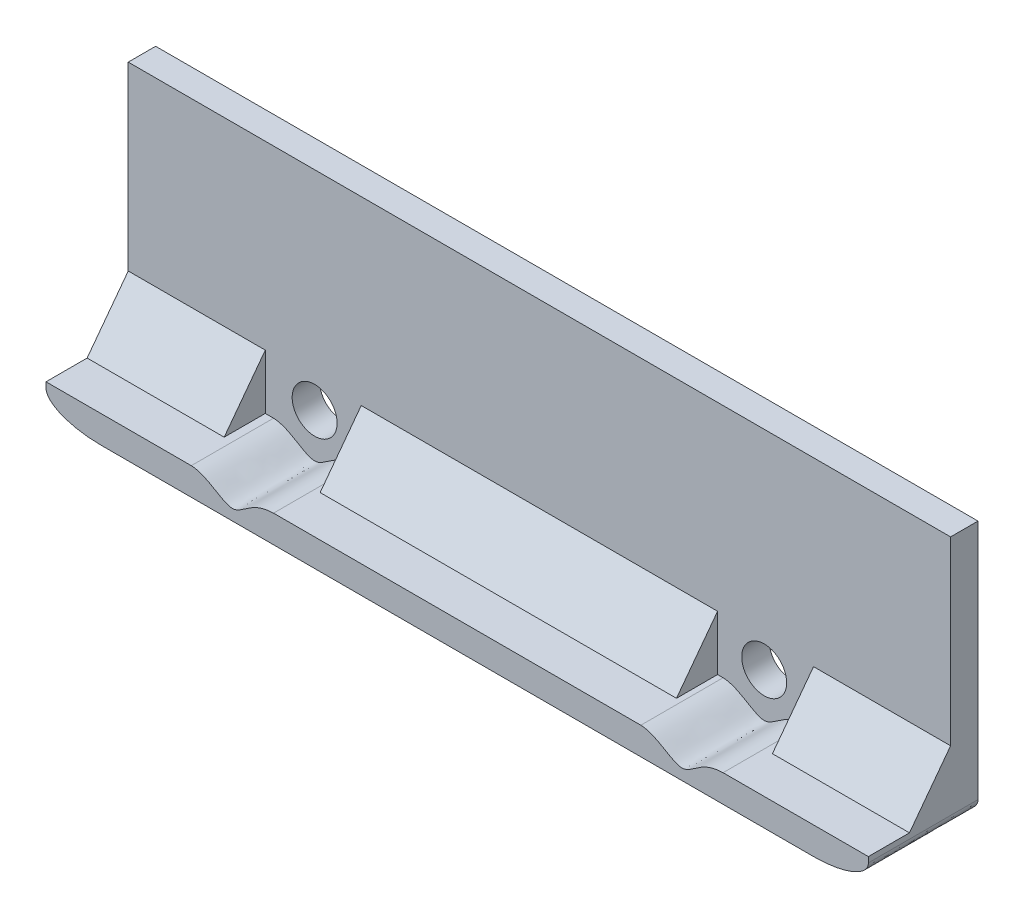
SolidWorks part; units mm, degrees
ref_plane "Front Plane" through (0, 0, 0) normal (0, 0, 1) x (1, 0, 0)
ref_plane "Top Plane" through (0, 0, 0) normal (0, 1, 0) x (1, 0, 0)
ref_plane "Right Plane" through (0, 0, 0) normal (1, 0, 0) x (0, 0, -1)
sketch "Sketch1" plane through (0, 0, 0) normal (0, 0, 1) x (1, 0, 0)
  line L0 (11.055, 0) -> (-11.055, 0) construction
  line L1 (-75, 0) -> (75, 0)
  line L2 (-75, 0) -> (-75, 48)
  line L3 (-75, 48) -> (75, 48)
  line L4 (75, 0) -> (75, 48)
  line L5 (0, 70.9447) -> (0, -59.6077) construction
  circle A0 centre (-41, 10) radius 4.1
  circle A1 centre (41, 10) radius 4.1
  dimension "D4" = 8.2
  dimension "D5" = 8.2
  dimension "D1" = 150
  dimension "D2" = 82
  dimension "D3" = 10
  dimension "D6" = 48
extrude "Boss-Extrude1" add sketch "Sketch1" along normal blind 5
sketch "Sketch2" plane through (0, 0, 0) normal (0, 0, 1) x (1, 0, 0)
  line L0 (55, 0) -> (-55, 0) construction
  line L1 (-75, 0) -> (75, 0)
  line L2 (-75, 0) -> (-75, 5)
  line L3 (-75, 5) -> (75, 5)
  line L4 (75, 0) -> (75, 5)
  line L5 (75, 0) -> (75, 48) construction
  line L6 (-41, 14.1) -> (-41, 5.9) construction
  line L7 (41, 14.1) -> (41, 5.9) construction
  circle A0 centre (-41, 10) radius 4.1 construction
  circle A1 centre (41, 10) radius 4.1 construction
  spline S0 degree 3 poles (-48.5, 5) (-45.5232, 4.8951) (-40.329, -0.8951) (-37.8188, 4.8951) (-33.5, 5) knots 0 0 0 0 0.5 1 1 1 1
  spline S1 degree 3 poles (33.5, 5) (36.4768, 4.8951) (41.671, -0.8951) (44.1812, 4.8951) (48.5, 5) knots 0 0 0 0 0.5 1 1 1 1
  dimension "D1" = 5
  dimension "D2" = 150
  dimension "D3" = 3
  dimension "D4" = 15
  dimension "D5" = 15
  dimension "D6" = 3
extrude "Boss-Extrude2" add sketch "Sketch2" along normal blind 20 contours S0 L3 L2 L1 L4 region at (0.0128, 2.4201, 0)
sketch "Sketch4" plane through (-75, 0, 0) normal (-1, 0, 0) x (0, 0, 1)
  line L0 (5, 5) -> (12.5, 5)
  line L1 (20, 5) -> (5, 5) construction
  line L2 (12.5, 5) -> (5, 15)
  line L3 (5, 15) -> (5, 5)
  dimension "D1" = 7.5
  dimension "D2" = 10
extrude "Boss-Extrude3" add sketch "Sketch4" against normal blind 25
extrude "Boss-Extrude4" add sketch "Sketch4<2>" along normal blind 25 from surface starting at face at (75, 17.6667, 8.3333)
sketch "Sketch4<2>" plane through (-75, 0, 0) normal (-1, 0, 0) x (0, 0, 1) same geometry as "Sketch4"
extrude "Boss-Extrude5" add sketch "Sketch4<3>" along normal mid plane 65 from surface starting at plane "Right Plane"
sketch "Sketch4<3>" plane through (-75, 0, 0) normal (-1, 0, 0) x (0, 0, 1) same geometry as "Sketch4"
fillet "Fillet5" radius 4 1 edges at (-75, 0, 10) second distance 10 first distance on face at (-75, 17.2857, 8.9286)
fillet "Fillet6" radius 10 1 edges at (75, 0, 10) second distance 4 first distance on face at (-30, 0, 12.5)
